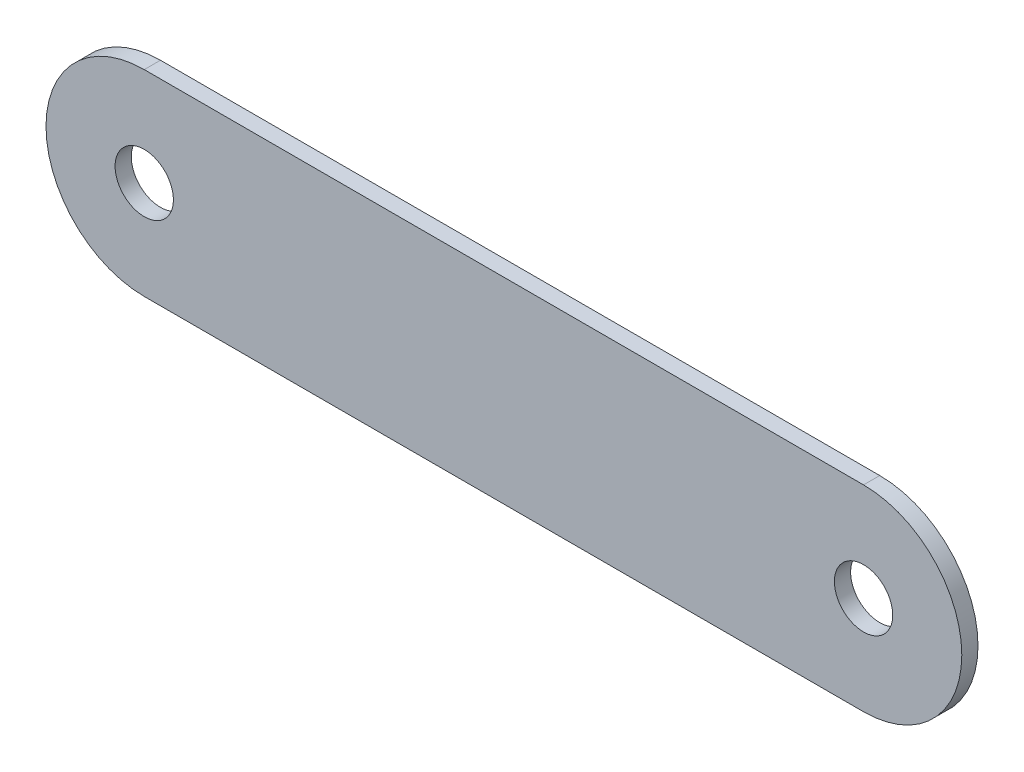
SolidWorks part; units mm, degrees
ref_plane "Front" through (0, 0, 0) normal (0, 0, 1) x (1, 0, 0)
ref_plane "Top" through (0, 0, 0) normal (0, 1, 0) x (1, 0, 0)
ref_plane "Right" through (0, 0, 0) normal (1, 0, 0) x (0, 0, -1)
sketch "Sketch1" plane through (0, 0, 0) normal (0, 0, 1) x (1, 0, 0)
  line L0 (-66.6, 0) -> (66.6, 0) construction
  line L1 (-66.6, 18.193) -> (66.6, 18.193)
  line L2 (-66.6, -18.193) -> (66.6, -18.193)
  arc A0 (-66.6, 18.193) -> (-66.6, -18.193) centre (-66.6, 0) ccw
  arc A1 (66.6, -18.193) -> (66.6, 18.193) centre (66.6, 0) ccw
  circle A2 centre (-66.6, 0) radius 5.4
  circle A4 centre (66.6, 0) radius 5.4
  point P2 (66.6, 0)
  point P3 (0, 0)
  point P9 (0, 0)
  point P10 (0, 0)
  point P14 (0, 0)
  dimension "D1" = 10.8
  dimension "D2" = 18.193
  dimension "D4" = 10.8
  dimension "D3" = 133.2
extrude "Boss-Extrude1" add sketch "Sketch1" along normal blind 3
